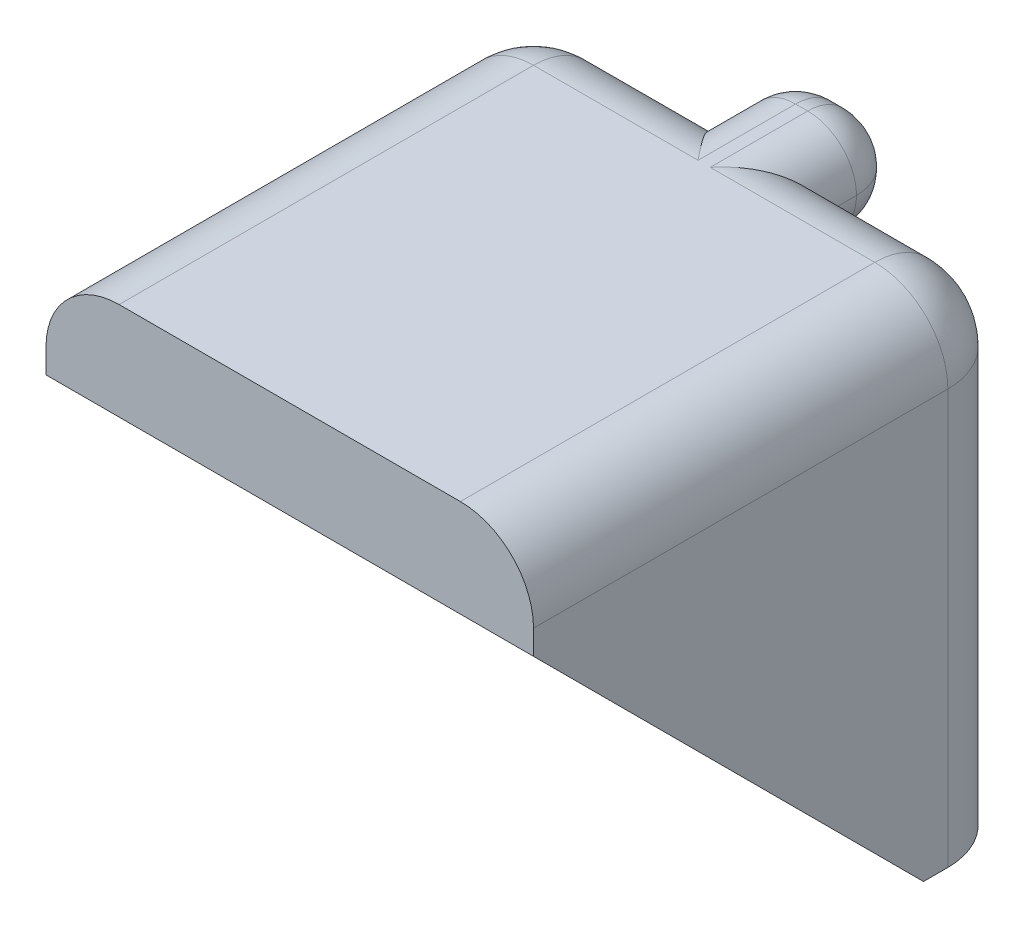
SolidWorks part; units mm, degrees
ref_plane "Plan de face" through (0, 0, 0) normal (0, 0, 1) x (1, 0, 0)
ref_plane "Plan de dessus" through (0, 0, 0) normal (0, 1, 0) x (1, 0, 0)
ref_plane "Plan de droite" through (0, 0, 0) normal (1, 0, 0) x (0, 0, -1)
sketch "Esquisse1" plane through (0, 0, 0) normal (0, 0, 1) x (1, 0, 0)
  line L0 (0, 10) -> (0, -10) construction
  line L1 (10, 10) -> (-10, 10)
  line L2 (10, 10) -> (10, -10)
  line L3 (10, -10) -> (-10, -10)
  line L4 (-10, 10) -> (-10, -10)
  line L5 (10, 10) -> (-10, -10) construction
  line L6 (10, -10) -> (-10, 10) construction
  circle A0 centre (0, -4) radius 2
  point P0 (0, 0)
  dimension "D3" = 4
  dimension "D1" = 20
  dimension "D2" = 20
  dimension "D4" = 6
extrude "Boss.-Extru.1" add sketch "Esquisse1" along normal blind 4
sketch "Esquisse2" plane through (0, 10, 0) normal (0, 1, 0) x (1, 0, 0)
  line L1 (-10, 0) -> (10, 0)
  line L2 (-10, 0) -> (-10, -20)
  line L3 (-10, -20) -> (10, -20)
  line L4 (10, 0) -> (10, -20)
  dimension "D1" = 20
  dimension "D2" = 20
extrude "Boss.-Extru.2" add sketch "Esquisse2" against normal blind 4
sketch "Esquisse3" plane through (-10, 0, 0) normal (-1, 0, 0) x (0, 0, 1)
  line L0 (4, -10) -> (20, 6)
  line L1 (20, 6) -> (4, 6)
  line L2 (4, 6) -> (4, -10)
extrude "Boss.-Extru.3" add sketch "Esquisse3" against normal blind 4
sketch "Esquisse4" plane through (10, 0, 0) normal (1, 0, 0) x (0, 0, -1)
  line L0 (-20, 6) -> (-4, 6)
  line L1 (-4, 6) -> (-4, -10)
  line L2 (-4, -10) -> (-20, 6)
extrude "Boss.-Extru.4" add sketch "Esquisse4" against normal blind 4
sketch "Esquisse5" plane through (0, 0, 0) normal (0, 0, -1) x (-1, 0, 0)
  line L0 (-10, 10) -> (10, 10) construction
  line L1 (0, 6) -> (0, 0) construction
  line L2 (-2.25, 10) -> (2.25, 10)
  line L3 (-2.25, 10) -> (-2.25, 6)
  line L4 (-2.25, 6) -> (2.25, 6)
  line L5 (2.25, 10) -> (2.25, 6)
  point P9 (0, -4)
  dimension "D1" = 4.5
  dimension "D2" = 10
extrude "Boss.-Extru.5" add sketch "Esquisse5" along normal blind 3
fillet "Congé1" radius 3 6 edges at (-10, 0, 0) (10, 0, 0) (-10, 10, 10) (-6.125, 10, 0) (6.125, 10, 0) (10, 10, 10)
fillet "Congé2" radius 2 6 edges at (0, 10, -3) (0, 6, -3) (-2.25, 6, -1.5) (2.25, 6, -1.5) (-2.25, 10, 0) (2.25, 10, 0)
